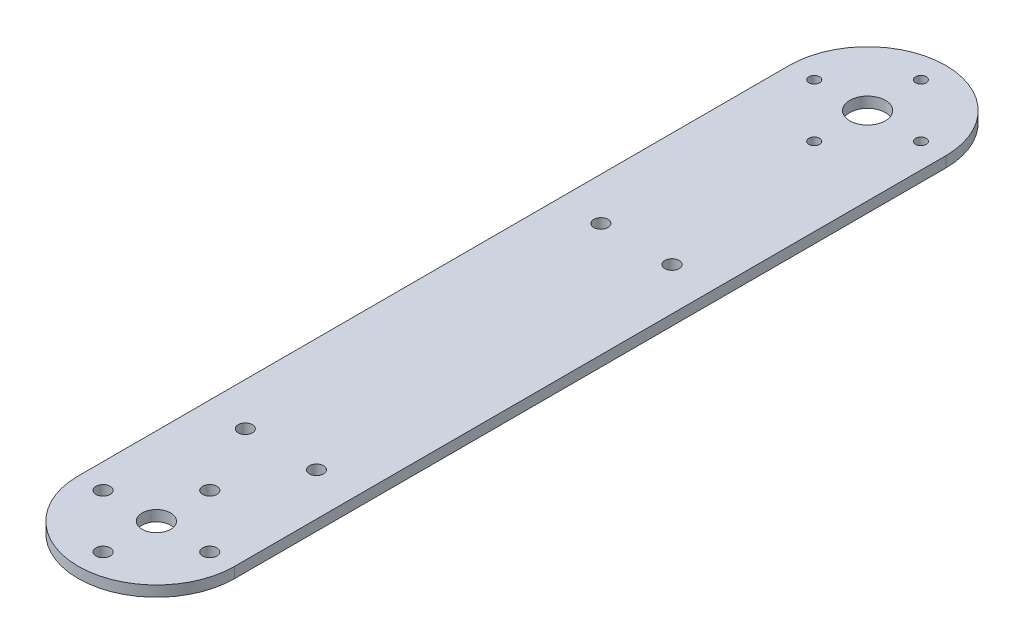
SolidWorks part; units mm, degrees
note: The reader was unsure of these and kept them because the rebuilt part matched: thickness of "基体-法兰1", "钣金6".
material "7075-T6，板材(SS)"
ref_plane "前视基准面" through (0, 0, 0) normal (0, 0, 1) x (1, 0, 0)
ref_plane "上视基准面" through (0, 0, 0) normal (0, 1, 0) x (1, 0, 0)
ref_plane "右视基准面" through (0, 0, 0) normal (1, 0, 0) x (0, 0, -1)
sketch "草图1" plane through (0, 0, 0) normal (0, 1, 0) x (1, 0, 0)
  line L0 (0, 0) -> (0, 200) construction
  line L1 (22, 200) -> (22, 0)
  line L2 (-22, 0) -> (-22, 200)
  arc A0 (-22, 0) -> (22, 0) centre (0, 0) ccw
  arc A1 (22, 200) -> (-22, 200) centre (0, 200) ccw
  circle A2 centre (0, 0) radius 4
  circle A4 centre (-10, 35) radius 2
  circle A5 centre (10, 35) radius 2
  circle A6 centre (-10, 135) radius 2
  circle A7 centre (10, 135) radius 2
  circle A8 centre (0, 200) radius 5
  circle A9 centre (0, 215) radius 1.5
  circle A10 centre (15, 200) radius 1.5
  circle A11 centre (0, 185) radius 1.5
  circle A12 centre (-15, 200) radius 1.5
  circle A18 centre (0, 15) radius 2
  circle A19 centre (15, 0) radius 2
  circle A20 centre (0, -15) radius 2
  circle A21 centre (-15, 0) radius 2
  point P19 (0, 15)
  point P28 (0, 200)
  point P37 (0, 0)
  point P41 (0, 0)
  dimension "D1" = 44
  dimension "D2" = 44
  dimension "D6" = 8
  dimension "D7" = 4
  dimension "D8" = 4
  dimension "D13" = 4
  dimension "D14" = 4
  dimension "D18" = 100
  dimension "D19" = 10
  dimension "D20" = 3
  dimension "D22" = 4
  dimension "D24" = 15
  dimension "D25" = 4
  dimension "D3" = 200
  dimension "D4" = 200
  dimension "D5" = 200
  dimension "D9" = 10
  dimension "D10" = 10
  dimension "D11" = 35
  dimension "D12" = 35
  dimension "D15" = 10
  dimension "D16" = 10
  dimension "D17" = 100
  dimension "D21" = 15
  dimension "D23" = 15
base flange "基体-法兰1" sketch "草图1" thickness 3 reverse thickness direction no parameters "D1"=0.7366
sketch "折弯-线1" [suppressed] plane through (0, 0, 0) normal (0, 1, 0) x (1, 0, 0)
sketch "边界框1" [suppressed] plane through (0, 0, 0) normal (0, 1, 0) x (1, 0, 0)
sheet metal parameters "钣金6" thickness 3 parameters "D1"=0.7366
flat pattern "平板型式6" [suppressed]
sketch "折弯-线2" plane through (0, 0, 0) normal (0, 1, 0) x (1, 0, 0)
sketch3d "边界框2" [suppressed]
  line L0 (-22, 22, 0) -> (-22, -222, 0) construction
  line L1 (22, 22, 0) -> (22, -222, 0) construction
  line L2 (-22, 22, 0) -> (22, 22, 0) construction
  line L3 (-22, -222, 0) -> (22, -222, 0) construction
